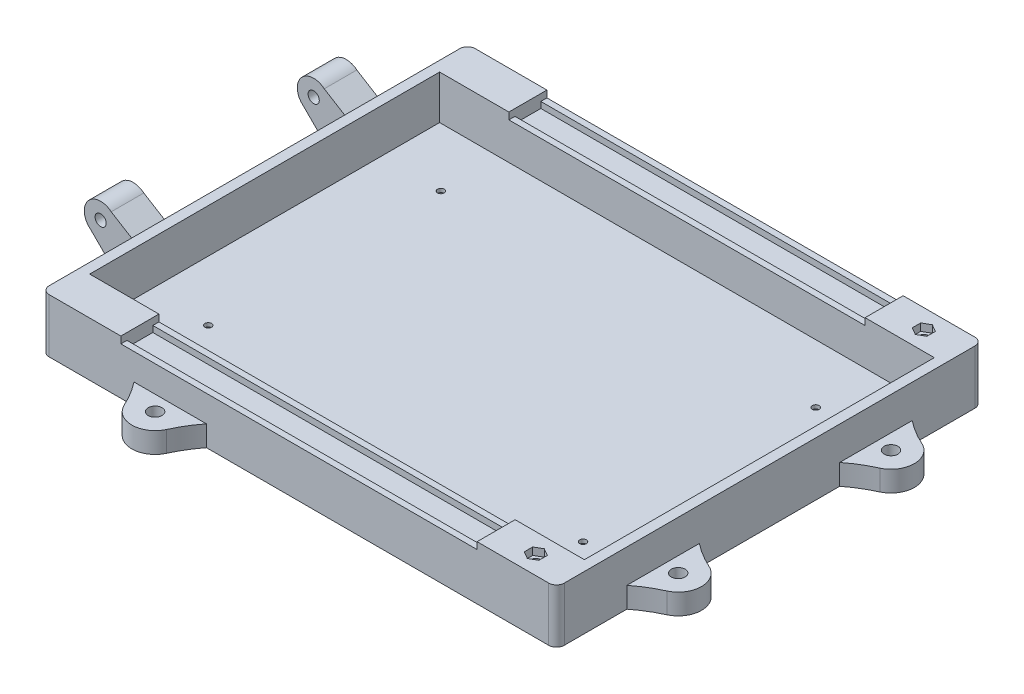
SolidWorks part; units mm, degrees
ref_plane "Front Plane" through (0, 0, 0) normal (0, 0, 1) x (1, 0, 0)
ref_plane "Top Plane" through (0, 0, 0) normal (0, 1, 0) x (1, 0, 0)
ref_plane "Right Plane" through (0, 0, 0) normal (1, 0, 0) x (0, 0, -1)
sketch "Sketch18" plane through (0, 0, 0) normal (0, 1, 0) x (1, 0, 0)
  line L1 (-126.52, -85.96) -> (126.52, -85.96)
  line L2 (-126.52, -85.96) -> (-126.52, 85.96)
  line L3 (-126.52, 85.96) -> (126.52, 85.96)
  line L4 (126.52, -85.96) -> (126.52, 85.96)
  line L5 (-126.52, -85.96) -> (126.52, 85.96) construction
  line L6 (-126.52, 85.96) -> (126.52, -85.96) construction
  point P0 (0, 0)
  dimension "D1" = 171.92
  dimension "D2" = 253.04
extrude "Boss-Extrude6" add sketch "Sketch18" along normal blind 26.5
sketch "Sketch20" plane through (0, 26.5, 0) normal (0, 1, 0) x (1, 0, 0)
  line L0 (126.52, 85.96) -> (-126.52, 85.96) construction
  line L1 (121.52, -85.96) -> (-121.52, -85.96)
  line L2 (121.52, -85.96) -> (121.52, 85.96)
  line L3 (121.52, 85.96) -> (-121.52, 85.96)
  line L4 (-121.52, -85.96) -> (-121.52, 85.96)
  line L5 (121.52, -85.96) -> (-121.52, 85.96) construction
  line L6 (121.52, 85.96) -> (-121.52, -85.96) construction
  point P0 (0, 0)
  dimension "D1" = 243.04
extrude "Cut-Extrude6" cut sketch "Sketch20" against normal blind 21.5
sketch "Sketch22" plane through (0, 0, 0) normal (0, 1, 0) x (1, 0, 0)
  line L1 (-126.52, -85.96) -> (126.52, -85.96)
  line L2 (-126.52, -85.96) -> (-126.52, -104.66)
  line L3 (-126.52, -104.66) -> (126.52, -104.66)
  line L4 (126.52, -85.96) -> (126.52, -104.66)
  dimension "D1" = 18.7
extrude "Boss-Extrude7" add sketch "Sketch22" along normal blind 26.5
sketch "Sketch23" plane through (0, 0, 0) normal (0, 1, 0) x (1, 0, 0)
  line L1 (126.52, 85.96) -> (-126.52, 85.96)
  line L2 (126.52, 85.96) -> (126.52, 104.66)
  line L3 (126.52, 104.66) -> (-126.52, 104.66)
  line L4 (-126.52, 85.96) -> (-126.52, 104.66)
  dimension "D1" = 18.7
extrude "Boss-Extrude8" add sketch "Sketch23" along normal blind 26.5
sketch "Sketch24" plane through (0, 26.5, 0) normal (0, 1, 0) x (1, 0, 0)
  line L0 (-121.52, 85.96) -> (121.52, 85.96) construction
  line L1 (-87.5, 104.66) -> (87.5, 104.66)
  line L2 (-87.5, 104.66) -> (-87.5, 85.96)
  line L3 (-87.5, 85.96) -> (87.5, 85.96)
  line L4 (87.5, 104.66) -> (87.5, 85.96)
  point P4 (0, 85.96)
  dimension "D1" = 18.7
  dimension "D2" = 175
extrude "Cut-Extrude7" cut sketch "Sketch24" against normal blind 3.35
sketch "Sketch25" plane through (0, 26.5, 0) normal (0, 1, 0) x (1, 0, 0)
  line L0 (121.52, -85.96) -> (-121.52, -85.96) construction
  line L1 (-87.5, -85.96) -> (87.5, -85.96)
  line L2 (-87.5, -85.96) -> (-87.5, -104.66)
  line L3 (-87.5, -104.66) -> (87.5, -104.66)
  line L4 (87.5, -85.96) -> (87.5, -104.66)
  point P4 (0, -85.96)
  dimension "D1" = 175
  dimension "D2" = 18.7
extrude "Cut-Extrude8" cut sketch "Sketch25" against normal blind 3.35
ref_point "Point2"
ref_point "Point3"
sketch "Sketch27" plane through (0, 23.15, 0) normal (0, 1, 0) x (1, 0, 0)
  line L0 (-87.5, -85.96) -> (-87.5, -104.66) construction
  line L1 (87.5, -88.96) -> (-87.5, -88.96)
  line L2 (87.5, -88.96) -> (87.5, -101.66)
  line L3 (87.5, -101.66) -> (-87.5, -101.66)
  line L4 (-87.5, -88.96) -> (-87.5, -101.66)
  line L5 (87.5, -88.96) -> (-87.5, -101.66) construction
  line L6 (87.5, -101.66) -> (-87.5, -88.96) construction
  point P0 (0, -95.31)
  dimension "D1" = 12.7
extrude "Cut-Extrude9" cut sketch "Sketch27" against normal blind 3
sketch "Sketch28" plane through (0, 23.15, 0) normal (0, 1, 0) x (1, 0, 0)
  line L0 (-87.5, 104.66) -> (-87.5, 85.96) construction
  line L1 (87.5, 88.96) -> (-87.5, 88.96)
  line L2 (87.5, 88.96) -> (87.5, 101.66)
  line L3 (87.5, 101.66) -> (-87.5, 101.66)
  line L4 (-87.5, 88.96) -> (-87.5, 101.66)
  line L5 (87.5, 88.96) -> (-87.5, 101.66) construction
  line L6 (87.5, 101.66) -> (-87.5, 88.96) construction
  point P0 (0, 95.31)
  dimension "D1" = 12.7
extrude "Cut-Extrude10" cut sketch "Sketch28" against normal blind 3
sketch "Sketch29" plane through (0, 5, 0) normal (0, 1, 0) x (1, 0, 0)
  line L1 (96.52, -60.96) -> (-96.52, -60.96)
  line L2 (96.52, -60.96) -> (96.52, 60.96)
  line L3 (96.52, 60.96) -> (-96.52, 60.96)
  line L4 (-96.52, -60.96) -> (-96.52, 60.96)
  line L5 (96.52, -60.96) -> (-96.52, 60.96) construction
  line L6 (96.52, 60.96) -> (-96.52, -60.96) construction
  point P0 (0, 0)
  point P6 (-92.07, 57.15)
  point P9 (92.07, 57.15)
  point P12 (92.07, -57.15)
  point P15 (-92.07, -57.15)
  dimension "D1" = 193.04
  dimension "D2" = 121.92
  dimension "D3" = 3.81
  dimension "D4" = 4.45
  dimension "D6" = 3.81
  dimension "D7" = 4.45
  dimension "D9" = 4.45
  dimension "D10" = 3.81
  dimension "D12" = 3.81
  dimension "D13" = 4.45
sketch "Sketch31" plane through (0, 5, 0) normal (0, 1, 0) x (1, 0, 0)
  circle A0 centre (-92.07, 57.15) radius 1.65
  circle A1 centre (92.07, 57.15) radius 1.65
  circle A2 centre (92.07, -57.15) radius 1.65
  circle A3 centre (-92.07, -57.15) radius 1.65
  dimension "D1" = 3.3
  dimension "D2" = 3.3
  dimension "D3" = 3.3
  dimension "D4" = 3.3
extrude "Cut-Extrude15" cut sketch "Sketch31" against normal blind 1.825
sketch "Sketch33" plane through (0, 0, 0) normal (0, -1, 0) x (1, 0, 0)
  line L0 (-96.52, 60.96) -> (-96.52, -60.96) construction
  line L1 (-88.939, -58.9577) -> (-88.939, -55.3423)
  line L2 (-88.939, -55.3423) -> (-92.07, -53.5346)
  line L3 (-92.07, -53.5346) -> (-95.201, -55.3423)
  line L4 (-95.201, -55.3423) -> (-95.201, -58.9577)
  line L5 (-95.201, -58.9577) -> (-92.07, -60.7654)
  line L6 (-92.07, -60.7654) -> (-88.939, -58.9577)
  line L7 (96.52, 60.96) -> (96.52, -60.96) construction
  line L8 (95.201, -58.9577) -> (95.201, -55.3423)
  line L9 (95.201, -55.3423) -> (92.07, -53.5346)
  line L10 (92.07, -53.5346) -> (88.939, -55.3423)
  line L11 (88.939, -55.3423) -> (88.939, -58.9577)
  line L12 (88.939, -58.9577) -> (92.07, -60.7654)
  line L13 (92.07, -60.7654) -> (95.201, -58.9577)
  line L15 (-88.939, 58.9577) -> (-92.07, 60.7654)
  line L16 (-92.07, 60.7654) -> (-95.201, 58.9577)
  line L17 (-95.201, 58.9577) -> (-95.201, 55.3423)
  line L18 (-95.201, 55.3423) -> (-92.07, 53.5346)
  line L19 (-92.07, 53.5346) -> (-88.939, 55.3423)
  line L20 (-88.939, 55.3423) -> (-88.939, 58.9577)
  line L21 (88.939, 58.9577) -> (88.939, 55.3423)
  line L22 (88.939, 55.3423) -> (92.07, 53.5346)
  line L23 (92.07, 53.5346) -> (95.201, 55.3423)
  line L24 (95.201, 55.3423) -> (95.201, 58.9577)
  line L25 (95.201, 58.9577) -> (92.07, 60.7654)
  line L26 (92.07, 60.7654) -> (88.939, 58.9577)
  circle A0 centre (-92.07, -57.15) radius 3.131 construction
  circle A1 centre (92.07, -57.15) radius 3.131 construction
  circle A2 centre (-92.07, 57.15) radius 3.131 construction
  circle A3 centre (92.07, 57.15) radius 3.131 construction
  dimension "D3" = 3.6154
  dimension "D1" = 3.6154
  dimension "D2" = 3.6154
  dimension "D4" = 3.6154
extrude "Cut-Extrude17" cut sketch "Sketch33" against normal blind 3.175
ref_plane "Plane5" through (0, 0, -52.33) normal (0, 0, 1) x (1, 0, 0)
ref_plane "Plane6" through (0, 0, 0) normal (0, 0, 1) x (1, 0, 0)
sketch "Sketch38" plane through (0, 0, -52.33) normal (0, 0, 1) x (1, 0, 0)
  line L0 (-126.52, 0) -> (-146.9559, 20.3526)
  line L5 (-126.52, 26.5) -> (-126.52, 0)
  line L6 (-126.52, 26.5) -> (-136.5621, 32.6474)
  arc A0 (-136.5621, 32.6474) -> (-146.9559, 20.3526) centre (-141.759, 26.5) ccw
  circle A1 centre (-141.759, 26.5) radius 2.75
  dimension "D1" = 16.0995
  dimension "D4" = 5.5
  dimension "D2" = 28.8418
  dimension "D3" = 11.7743
extrude "Boss-Extrude12" add sketch "Sketch38" along normal blind 8 and the other way blind 8
mirror "Mirror2" about plane through (0, 0, 0) normal (0, 0, 1) of "Boss-Extrude12"
sketch "Sketch39" plane through (0, 26.5, 0) normal (0, 1, 0) x (1, 0, 0)
  line L0 (87.5, 85.96) -> (87.5, 104.66) construction
  line L1 (126.52, 104.66) -> (87.5, 104.66) construction
  circle A0 centre (107.01, 95.31) radius 2.2
  point P5 (87.5, 95.31)
  point P10 (107.01, 104.66)
  dimension "D1" = 4.4
extrude "Cut-Extrude18" cut sketch "Sketch39" against normal blind 26.5
sketch "Sketch40" plane through (0, 0, 0) normal (0, -1, 0) x (1, 0, 0)
  circle A0 centre (107.01, -95.31) radius 4.4
  dimension "D1" = 8.8
extrude "Cut-Extrude19" cut sketch "Sketch40" against normal blind 20.9
mirror "Mirror3" about plane through (0, 0, 0) normal (0, 0, 1) of "Cut-Extrude18"
mirror "Mirror4" about plane through (0, 0, 0) normal (0, 0, 1) of "Cut-Extrude19"
fillet "Fillet1" radius 3.81 4 edges at (126.52, 13.25, 104.66) (-126.52, 13.25, 104.66) (-126.52, 13.25, -104.66) (126.52, 13.25, -104.66)
sketch "Sketch41" plane through (0, 26.5, 0) normal (0, 1, 0) x (1, 0, 0)
  line L1 (107.01, -91.1531) -> (103.41, -93.2315)
  line L2 (103.41, -93.2315) -> (103.41, -97.3885)
  line L3 (103.41, -97.3885) -> (107.01, -99.4669)
  line L4 (107.01, -99.4669) -> (110.61, -97.3885)
  line L5 (110.61, -97.3885) -> (110.61, -93.2315)
  line L6 (110.61, -93.2315) -> (107.01, -91.1531)
  circle A0 centre (107.01, -95.31) radius 3.6 construction
  point P1 (105.21, -98.4277)
  dimension "D1" = 7.2
extrude "Cut-Extrude20" cut sketch "Sketch41" against normal blind 3.6
mirror "Mirror5" about plane through (0, 0, 0) normal (0, 0, 1) of "Cut-Extrude20"
sketch "Sketch45" plane through (0, 0, 0) normal (0, -1, 0) x (1, 0, 0)
  line L0 (-122.71, 104.66) -> (122.71, 104.66) construction
  line L2 (-57.7037, 115.2837) -> (-63.26, 118.4916) construction
  line L3 (-63.26, 118.4916) -> (-68.8162, 115.2837) construction
  line L4 (-68.8162, 115.2837) -> (-68.8162, 108.8679) construction
  line L5 (-68.8162, 108.8679) -> (-63.26, 105.66) construction
  line L6 (-63.26, 105.66) -> (-57.7037, 108.8679) construction
  line L7 (-57.7037, 108.8679) -> (-57.7037, 115.2837) construction
  line L9 (-126.52, 60.33) -> (-126.52, 100.85) construction
  arc A0 (-81.0627, 104.66) -> (-71.4921, 122.3531) centre (-127.3207, 141.117) ccw
  arc A1 (-55.0279, 122.3531) -> (-71.4921, 122.3531) centre (-63.26, 119.5862) ccw
  arc A2 (-45.4573, 104.66) -> (-55.0279, 122.3531) centre (0.8007, 141.117) cw
  circle A3 centre (-63.26, 112.0758) radius 5.5562 construction
  circle A4 centre (-63.26, 112.0758) radius 6.4158 construction
  circle A5 centre (-63.26, 112.0758) radius 3.3782
  arc A6 (-73.613, 116.9426) -> (-52.907, 116.9426) centre (-63.26, 112.076) cw
  point P24 (-63.26, 123.5158)
  line M36 (122.71, 104.66) -> (-122.71, 104.66)
  dimension "D2" = 6.7564
  dimension "D5" = 11.44
  dimension "D1" = 11.1125
  dimension "D3" = 1
  dimension "D4" = 63.26
ref_plane "Plane7" through (-63.26, 0, 0) normal (-1, 0, 0) x (0, 0, 1)
ref_axis "Axis2" through (0, 0, 104.66) along (0, 0, 1)
extrude "Boss-Extrude13" add sketch "Sketch45" against normal blind 10.16 contours A2 A1 A0 A5 M36 region at (-76.6175, 0, 110.3644)
ref_plane "Plane8" through (0, 0, 0) normal (-1, 0, 0) x (0, 0, 1)
sketch "Sketch47" plane through (0, 0, 0) normal (0, -1, 0) x (1, 0, 0)
  line L0 (126.52, 100.85) -> (126.52, -100.85) construction
  line L2 (137.1437, -57.8351) -> (140.3516, -52.2789) construction
  line L3 (140.3516, -52.2789) -> (137.1437, -46.7226) construction
  line L4 (137.1437, -46.7226) -> (130.7279, -46.7226) construction
  line L5 (130.7279, -46.7226) -> (127.52, -52.2789) construction
  line L6 (127.52, -52.2789) -> (130.7279, -57.8351) construction
  line L7 (130.7279, -57.8351) -> (137.1437, -57.8351) construction
  arc A0 (126.52, -34.4761) -> (138.8026, -41.9258) centre (162.977, 11.7819) ccw
  arc A2 (126.52, -70.0816) -> (138.8026, -62.6319) centre (162.977, -116.3396) cw
  circle A3 centre (133.9358, -52.2789) radius 5.5562 construction
  circle A4 centre (133.9358, -52.2789) radius 6.4158 construction
  circle A5 centre (133.9358, -52.2789) radius 3.3782
  arc A6 (138.8026, -41.9258) -> (138.8026, -62.6319) centre (133.936, -52.2789) cw
  point P24 (145.3758, -52.2789)
  line M111 (126.52, -100.85) -> (126.52, 100.85)
  dimension "D2" = 6.7564
  dimension "D5" = 11.44
  dimension "D1" = 11.1125
extrude "Boss-Extrude14" add sketch "Sketch47" against normal blind 10.16 contours A6 A0 A2 A5 M111 region at (132.2244, 0, -38.9214)
mirror "Mirror8" about plane through (0, 0, 0) normal (0, 0, 1) of "Boss-Extrude14"
